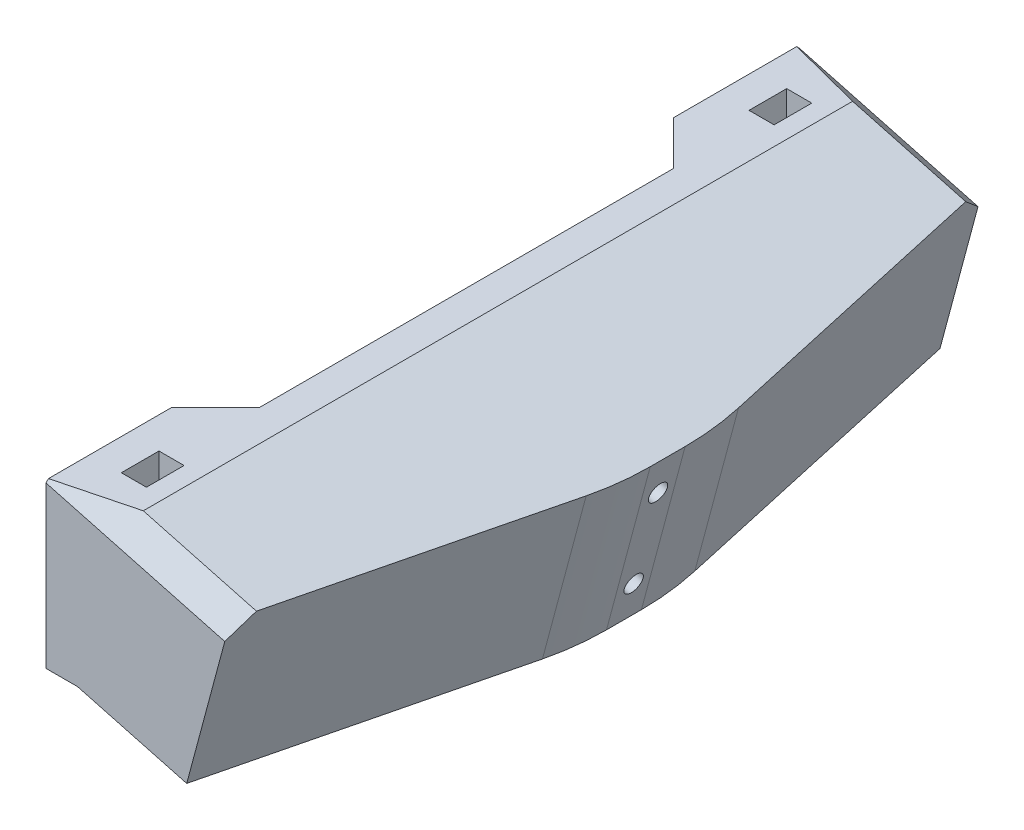
SolidWorks part; units mm, degrees
ref_plane "Front" through (0, 0, 0) normal (0, 0, 1) x (1, 0, 0)
ref_plane "Top" through (0, 0, 0) normal (0, 1, 0) x (1, 0, 0)
ref_plane "Right" through (0, 0, 0) normal (1, 0, 0) x (0, 0, -1)
sketch "Sketch1" plane through (0, 0, 0) normal (0, 0, 1) x (1, 0, 0)
  line L0 (0, 0) -> (0, 26)
  line L1 (0, 26) -> (12, 26)
  line L2 (12, 26) -> (29.3867, 21.3413)
  line L3 (29.3867, 21.3413) -> (22.42, -4.6587)
  line L4 (12, 26) -> (5.0333, 0)
  line L5 (0, 0) -> (5.0333, 0)
  line L6 (5.0333, 0) -> (22.42, -4.6587)
  line L7 (5.0333, 0) -> (5.0333, -8.6951) construction
  dimension "D3" = 18
  dimension "D1" = 26
  dimension "D2" = 12
  dimension "D4" = 75
extrude "Boss-Extrude1" add sketch "Sketch1" against normal blind 120 contours L4 L6 L3 L2 | L0 L5 L4 L1 region at (4.4958, 14.7723, 0) region at (17.21, 10.6706, 0)
sketch "Sketch3" plane through (7.3038, 27.2583, 0) normal (0.2588, 0.9659, 0) x (0.9659, -0.2588, 0)
  line L0 (22.8618, 0) -> (32.8618, 52.5)
  line L1 (32.8618, 52.5) -> (32.8618, 67.5)
  line L2 (32.8618, 67.5) -> (22.8618, 120)
  line L3 (32.8618, 60) -> (22.8618, 60) construction
  line L4 (22.8618, 120) -> (22.8618, 0) construction
  line L5 (22.8618, 120) -> (22.8618, 0)
  dimension "D1" = 10
  dimension "D2" = 15
extrude "Boss-Extrude2" add sketch "Sketch3" against normal up to surface (26.9172 mm away) up to face at (13.7267, -2.3294, -60)
sketch "Sketch6" plane through (0, 26, 0) normal (0, 1, 0) x (1, 0, 0)
  line L0 (0, 100) -> (7, 93)
  line L21 (0, 120) -> (0, 0) construction
  line L22 (7, 93) -> (7, 27)
  line L25 (7, 27) -> (0, 20)
  line L26 (0, 120) -> (12, 120) construction
  line L31 (0, 100) -> (0, 20)
  dimension "D1" = 45
  dimension "D2" = 45
  dimension "D3" = 7
  dimension "D4" = 20
  dimension "D5" = 20
extrude "Cut-Extrude3" cut sketch "Sketch6" against normal through all
sketch "Sketch7" plane through (0, 0, 0) normal (-1, 0, 0) x (0, 0, 1)
  line L0 (-120, 0) -> (-120, 26) construction
  line L1 (0, 0) -> (0, 26) construction
  line L2 (-120, 0) -> (-100, 0) construction
  circle A0 centre (-110, 15) radius 1.55
  circle A1 centre (-10, 15) radius 1.55
  point P4 (0, 0)
  dimension "D1" = 3.1
  dimension "D2" = 3.1
  dimension "D4" = 10
  dimension "D5" = 15
  dimension "D3" = 10
extrude "Cut-Extrude4" cut sketch "Sketch7" against normal blind 10
ref_plane "Plane2" through (5, 0, 0) normal (-1, 0, 0) x (0, 0, 1)
sketch "Sketch8" plane through (5, 0, 0) normal (-1, 0, 0) x (0, 0, 1)
  line L0 (-113, 16.7321) -> (-113, 26)
  line L1 (-111.5, 17.5981) -> (-113, 16.7321)
  line L2 (-113, 16.7321) -> (-113, 13.2679)
  line L3 (-113, 13.2679) -> (-110, 11.5359)
  line L4 (-110, 11.5359) -> (-107, 13.2679)
  line L5 (-107, 13.2679) -> (-107, 16.7321)
  line L6 (-107, 16.7321) -> (-108.5, 17.5981)
  line L7 (-120, 26) -> (-100, 26) construction
  line L8 (-113, 26) -> (-107, 26)
  line L9 (-107, 26) -> (-107, 16.7321)
  line L10 (-60, 26) -> (-60, 24.3172) construction
  line L11 (-27, 26) -> (-93, 26) construction
  line L12 (-13, 26) -> (-13, 16.7321)
  line L13 (-7, 26) -> (-13, 26)
  line L14 (-13, 16.7321) -> (-11.5, 17.5981)
  line L15 (-13, 13.2679) -> (-13, 16.7321)
  line L16 (-10, 11.5359) -> (-13, 13.2679)
  line L17 (-7, 13.2679) -> (-10, 11.5359)
  line L18 (-7, 16.7321) -> (-7, 13.2679)
  line L19 (-8.5, 17.5981) -> (-7, 16.7321)
  line L20 (-7, 16.7321) -> (-7, 26)
  circle A0 centre (-110, 15) radius 3 construction
  circle A1 centre (-10, 15) radius 3 construction
  dimension "D1" = 6
extrude "Cut-Extrude5" cut sketch "Sketch8" against normal blind 4 contours L9 L8 L0 L2 L3 L4 L5 | L20 L13 L12 L15 L16 L17 L18 region at (5, 19.1918, -110) region at (5, 19.1918, -10)
fillet "Fillet1" radius 50 2 edges at (35.5626, 5.7531, -67.5) (35.5626, 5.7531, -52.5)
sketch "Sketch10" plane through (31.7421, -8.5053, 0) normal (0.9659, -0.2588, 0) x (0, 0, -1)
  line L1 (62.7805, 14.7613) -> (57.2195, 14.7613) construction
  line L2 (62.7805, 1.3027) -> (62.7805, 28.2199) construction
  line L3 (60, 22.2613) -> (60, 7.2613) construction
  line L4 (57.2195, 28.2199) -> (57.2195, 1.3027) construction
  circle A0 centre (60, 22.2613) radius 1.5
  circle A1 centre (60, 7.2613) radius 1.5
  point P4 (60, 14.7613)
  point P11 (60, 14.7613)
  dimension "D1" = 3
  dimension "D2" = 3
  dimension "D3" = 15
extrude "Cut-Extrude6" cut sketch "Sketch10" against normal through all
chamfer "Chamfer4" distance 3.5 angle 45 2 edges at (20.6933, 23.6706, -120) (20.6933, 23.6706, 0)
ref_plane "Plane3" through (-2.0653, 0.5534, 0) normal (0.9659, -0.2588, 0) x (0, 0, -1)
sketch "Sketch12" plane through (-2.0653, 0.5534, 0) normal (0.9659, -0.2588, 0) x (0, 0, -1)
  circle A0 centre (60, 22.2613) radius 4
  circle A1 centre (60, 7.2613) radius 4
  dimension "D1" = 8
  dimension "D2" = 8
extrude "Cut-Extrude8" cut sketch "Sketch12" along normal blind 5 contours A0 region at (3.6963, 22.0562, -60)
extrude "Cut-Extrude9" cut sketch "Sketch12<3>" along normal blind 9 contours A1 region at (-0.186, 7.5673, -60)
sketch "Sketch12<3>" plane through (-2.0653, 0.5534, 0) normal (0.9659, -0.2588, 0) x (0, 0, -1) same geometry as "Sketch12"
